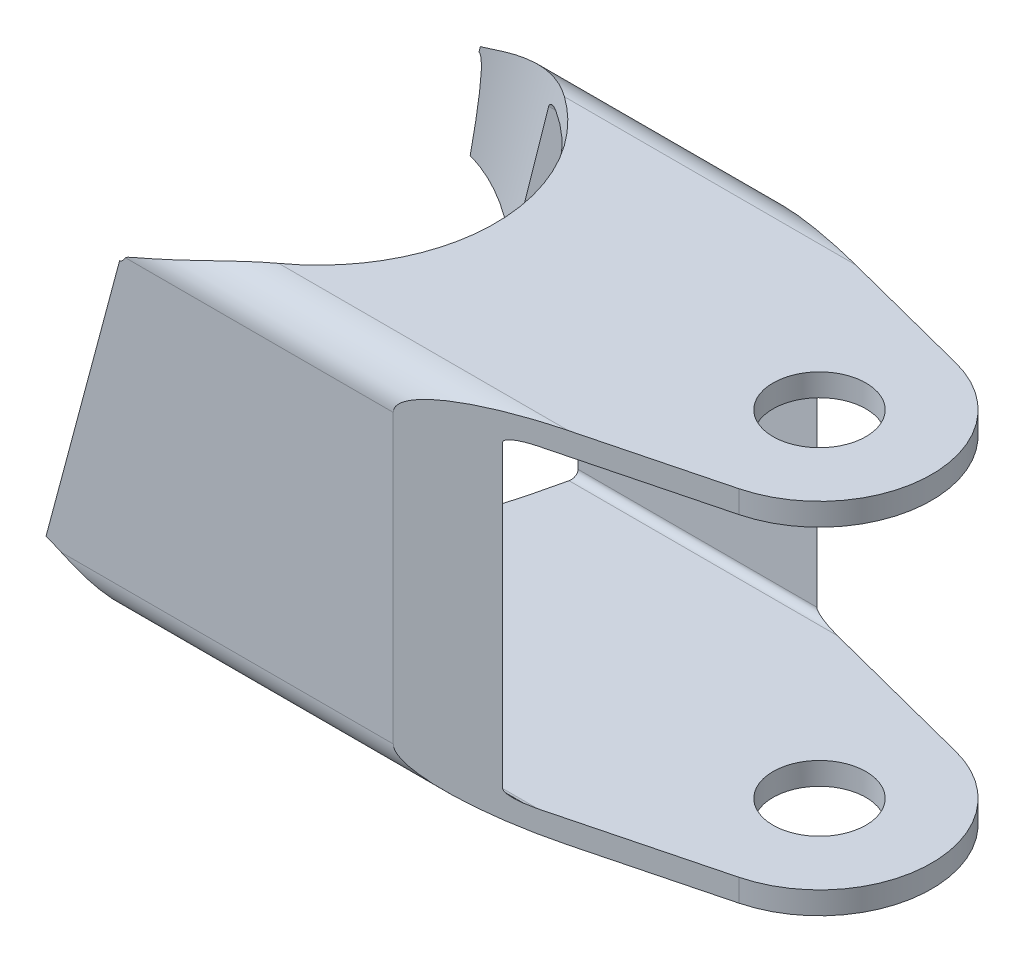
SolidWorks part; units mm, degrees
ref_plane "Front Plane" through (0, 0, 0) normal (0, 0, 1) x (1, 0, 0)
ref_plane "Top Plane" through (0, 0, 0) normal (0, 1, 0) x (1, 0, 0)
ref_plane "Right Plane" through (0, 0, 0) normal (1, 0, 0) x (0, 0, -1)
sketch "Sketch1" plane through (0, 0, 0) normal (1, 0, 0) x (0, 0, -1)
  line L1 (-10.16, 12.7) -> (10.16, 12.7)
  line L2 (-12.7, 10.16) -> (-12.7, -10.16)
  line L3 (-10.16, -12.7) -> (10.16, -12.7)
  line L4 (12.7, 10.16) -> (12.7, -10.16)
  arc A0 (-10.16, 12.7) -> (-12.7, 10.16) centre (-10.16, 10.16) ccw
  arc A1 (-10.16, -12.7) -> (-12.7, -10.16) centre (-10.16, -10.16) cw
  arc A2 (10.16, 12.7) -> (12.7, 10.16) centre (10.16, 10.16) cw
  arc A3 (12.7, -10.16) -> (10.16, -12.7) centre (10.16, -10.16) cw
  point P4 (0, -12.7)
  point P7 (0, 0)
  point P15 (12.7, 0)
  dimension "D3" = 2.54
  dimension "D4" = 2.54
  dimension "D5" = 2.54
  dimension "D6" = 2.54
  dimension "D1" = 25.4
  dimension "D2" = 20.32
extrude "Boss-Extrude1" add sketch "Sketch1" along normal blind 25.4 and the other way blind 34.925
sketch "Sketch11" plane through (25.4, 0, 0) normal (1, 0, 0) x (0, 0, -1)
  line L0 (-10.16, -12.7) -> (10.16, -12.7) construction
  line L1 (-10.6045, 11.1125) -> (10.6045, 11.1125)
  line L2 (-11.1125, 10.6045) -> (-11.1125, -10.6045)
  line L3 (-10.6045, -11.1125) -> (10.6045, -11.1125)
  line L4 (11.1125, 10.6045) -> (11.1125, -10.6045)
  line L5 (10.16, 12.7) -> (-10.16, 12.7) construction
  line L6 (12.7, -10.16) -> (12.7, 10.16) construction
  line L7 (-12.7, 10.16) -> (-12.7, -10.16) construction
  arc A0 (10.6045, 11.1125) -> (11.1125, 10.6045) centre (10.6045, 10.6045) cw
  arc A1 (10.6045, -11.1125) -> (11.1125, -10.6045) centre (10.6045, -10.6045) ccw
  arc A2 (-11.1125, -10.6045) -> (-10.6045, -11.1125) centre (-10.6045, -10.6045) ccw
  arc A3 (-10.6045, 11.1125) -> (-11.1125, 10.6045) centre (-10.6045, 10.6045) ccw
  dimension "D1" = 1.5875
  dimension "D2" = 1.5875
  dimension "D3" = 1.5875
  dimension "D4" = 1.5875
  dimension "D5" = 0.508
extrude "Cut-Extrude4" cut sketch "Sketch11" against normal through all
sketch "Sketch12" plane through (0, 12.7, 0) normal (0, 1, 0) x (1, 0, 0)
  line L1 (0, 12.7) -> (50.8, 12.7)
  line L2 (50.8, 12.7) -> (50.8, -12.7)
  line L12 (50.8, -12.7) -> (0, -12.7)
  line L13 (19.4444, -7.6861) -> (0, -12.7)
  line L14 (19.4444, 7.6861) -> (0, 12.7)
  line L15 (-34.925, -12.7) -> (25.4, -12.7) construction
  line L16 (-34.925, 12.7) -> (25.4, 12.7) construction
  line L18 (25.4, 10.16) -> (25.4, -10.16) construction
  arc A1 (19.4444, -7.6861) -> (19.4444, 7.6861) centre (17.4625, 0) ccw
  point P8 (18.1688, 9.2165)
  line M6 (-34.925, -10.16) -> (25.4, -10.16)
  line M7 (25.4, -10.16) -> (25.4, 10.16)
  line M8 (25.4, 10.16) -> (-34.925, 10.16)
  line M9 (-34.925, 10.16) -> (-34.925, -10.16)
  dimension "D2" = 50.8
  dimension "D1" = 17.4625
extrude "Cut-Extrude5" cut sketch "Sketch12" against normal through all contours M9 M8 M7 M6 | M7 M8 M9 | M6 M7 region at (34.888, 12.7, 0) region at (20.955, 12.7, -8.1283) region at (20.955, 12.7, 8.1283)
sketch "Sketch14" plane through (0, 12.7, 0) normal (0, 1, 0) x (1, 0, 0)
  circle A0 centre (17.4625, 0) radius 3.2893
  arc A2 (19.4444, -7.6861) -> (19.4444, 7.6861) centre (17.4625, 0) ccw construction
  point P0 (17.4625, 0)
  point P6 (25.4, 0)
  dimension "D2" = 6.5786
  dimension "D1" = 7.9375
  dimension "D3" = 17.4625
extrude "Cut-Extrude6" cut sketch "Sketch14" against normal through all
ref_axis "Axis1" through (-31.2379, -26.3737, 19.0157) along (0.2163, 0.431, -0.876)
ref_axis "Axis2" through (-19.5832, -18.2683, -63.4187) along (-0.1086, 0.0213, 0.9939)
ref_axis "Axis3" through (-26.408, -17.3467, -0.1201) along (0.1865, -0.9626, 0.1964)
ref_axis "Axis4" through (-73.2818, -4.4166, -0.2082) along (0.9661, -0.2581, 0)
ref_axis "Axis5" through (-29.0199, -26.3804, -0.2819) along (0.2581, 0.9661, 0.0075)
ref_point "Point5"
ref_point "Point3"
ref_point "Point1"
ref_point "Point4"
ref_point "Point2"
ref_plane "Plane1" through (-24.3765, -12.7, -8.7748) normal (0.2163, 0.431, -0.876) x (-0.9763, 0.0955, -0.1941)
ref_plane "Plane2" through (-25.1264, -17.1825, -12.7) normal (0.1086, -0.0213, -0.9939) x (-0.9941, -0.0023, -0.1086)
ref_plane "Plane3" through (-27.308, -12.7, -1.0681) normal (-0.1865, 0.9626, -0.1964) x (0.9825, 0.1827, -0.0373)
ref_plane "Plane4" through (-34.925, -14.6623, -0.2082) normal (0.9661, -0.2581, 0) x (0, 0, -1)
ref_plane "Plane5" through (-21.9733, 0, -0.0765) normal (0.2581, 0.9661, 0.0075) x (0.9661, -0.2581, -0.002)
sketch "Sketch15" plane through (-24.3765, -12.7, -8.7748) normal (0.2163, 0.431, -0.876) x (-0.9763, 0.0955, -0.1941)
  circle A0 centre (0, 0) radius 12.7
  dimension "D1" = 25.4
sketch "Sketch16" plane through (-25.1264, -17.1825, -12.7) normal (0.1086, -0.0213, -0.9939) x (-0.9941, -0.0023, -0.1086)
  circle A0 centre (0, 0) radius 12.7
  dimension "D1" = 25.4
sketch "Sketch17" plane through (-27.308, -12.7, -1.0681) normal (-0.1865, 0.9626, -0.1964) x (0.9825, 0.1827, -0.0373)
  circle A0 centre (0, 0) radius 12.7
  dimension "D1" = 25.4
sketch "Sketch18" plane through (-34.925, -14.6623, -0.2082) normal (0.9661, -0.2581, 0) x (0, 0, -1)
  circle A0 centre (0, 0) radius 12.7
  dimension "D1" = 25.4
sketch "Sketch19" plane through (-21.9733, 0, -0.0765) normal (0.2581, 0.9661, 0.0075) x (0.9661, -0.2581, -0.002)
  circle A0 centre (0, 0) radius 12.7
  dimension "D1" = 25.4
extrude "Cut-Extrude7" cut sketch "Sketch15" against normal blind 25.4 and the other way blind 25.4
extrude "Cut-Extrude9" cut sketch "Sketch17" against normal blind 12.7 and the other way blind 6.35
extrude "Cut-Extrude10" cut sketch "Sketch18" against normal blind 25.4 and the other way blind 6.35
extrude "Cut-Extrude11" cut sketch "Sketch19" against normal blind 25.4 and the other way blind 25.4
ref_axis "Axis6" through (-11.0875, 40.7532, 0.2407) along (-0.2581, -0.9661, -0.0075)
ref_plane "Plane6" through (-20.5099, 5.4785, 0) normal (0.9661, -0.2581, 0) x (-0.2581, -0.9661, -0.0075)
sketch "Sketch21" plane through (-20.5099, 5.4785, 0) normal (0.9661, -0.2581, 0) x (-0.2581, -0.9661, -0.0075)
  line L1 (27.536, -22.5267) -> (-27.536, -22.5267)
  line L2 (27.536, -22.5267) -> (27.536, 22.5267)
  line L3 (27.536, 22.5267) -> (-27.536, 22.5267)
  line L4 (-27.536, -22.5267) -> (-27.536, 22.5267)
  line L5 (27.536, -22.5267) -> (-27.536, 22.5267) construction
  line L6 (27.536, 22.5267) -> (-27.536, -22.5267) construction
  point P0 (0, 0)
extrude "Cut-Extrude12" cut sketch "Sketch21" against normal through all
